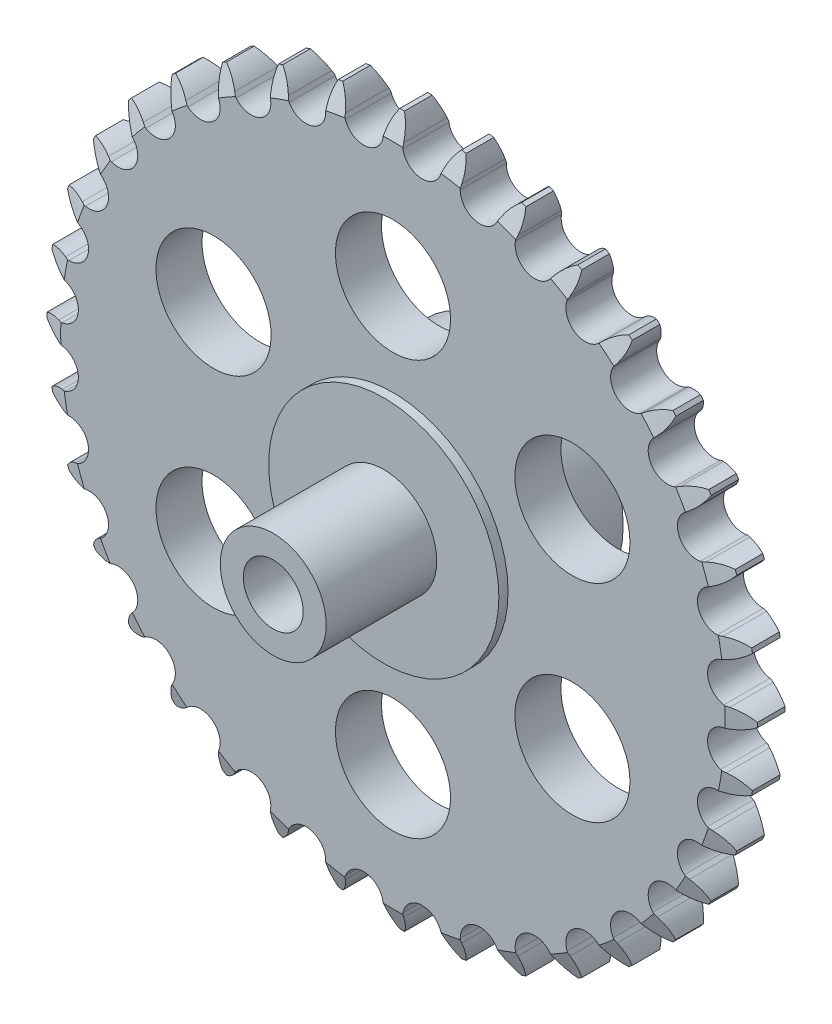
SolidWorks part; units mm, degrees
ref_plane "Front Plane" through (0, 0, 0) normal (0, 0, 1) x (1, 0, 0)
ref_plane "Top Plane" through (0, 0, 0) normal (0, 1, 0) x (1, 0, 0)
ref_plane "Right Plane" through (0, 0, 0) normal (1, 0, 0) x (0, 0, -1)
sketch "Sketch1" plane through (0, 0, 0) normal (0, 0, 1) x (1, 0, 0)
  line L0 (0, 0) -> (0, 72.8581) construction
  line L1 (-2.1568, 71.8581) -> (2.1568, 71.8581) construction
  line L2 (-2.1568, 71.8581) -> (-2.0429, 72.8581) construction
  line L3 (2.1568, 71.8581) -> (2.0429, 72.8581) construction
  line L4 (-2.0429, 72.8581) -> (2.0429, 72.8581) construction
  line L7 (-0.5, 77.163) -> (0.5, 77.163) construction
  circle A0 centre (0, 0) radius 72.8581 construction
  circle A1 centre (6.35, 72.5808) radius 4.255 construction
  circle A2 centre (-6.35, 72.5808) radius 4.255 construction
  circle A3 centre (0, 0) radius 68.6031 construction
  arc A4 (-2.0429, 72.8581) -> (-0.5, 77.163) centre (7.8928, 71.726) cw construction
  arc A5 (2.0429, 72.8581) -> (0.5, 77.163) centre (-7.8928, 71.726) ccw construction
  dimension "D1" = 13
  dimension "SprocketPitchDiameter" = 145.7162
  dimension "RollerDia" = 8.51
  dimension "D4" = 10
  dimension "ChainPitch" = 12.7
  dimension "D2" = 1
  dimension "D3" = 1
  dimension "D5" = 1
sketch "Sketch2" plane through (0, 0, 0) normal (0, 0, 1) x (1, 0, 0)
  circle A0 centre (0, 0) radius 68.6031 construction
  circle A1 centre (0, 0) radius 68.6031
extrude "Boss-Extrude1" add sketch "Sketch2" along normal mid plane 10
sketch "Sketch4" plane through (0, 0, 0) normal (0, 0, 1) x (1, 0, 0)
  line L0 (-0.5, 77.163) -> (0.5, 77.163) construction
  line L1 (-2.1568, 71.8581) -> (-2.0429, 72.8581) construction
  line L2 (2.1568, 71.8581) -> (2.0429, 72.8581) construction
  line L3 (-0.5, 77.163) -> (0.5, 77.163)
  line L4 (-2.1568, 71.8581) -> (-2.0429, 72.8581)
  line L5 (2.1568, 71.8581) -> (2.0429, 72.8581)
  circle A0 centre (0, 0) radius 68.6031 construction
  circle A1 centre (6.35, 72.5808) radius 4.255 construction
  circle A2 centre (-6.35, 72.5808) radius 4.255 construction
  arc A3 (2.0429, 72.8581) -> (0.5, 77.163) centre (-7.8928, 71.726) ccw construction
  arc A4 (-0.5, 77.163) -> (-2.0429, 72.8581) centre (7.8928, 71.726) ccw construction
  arc A5 (5.9792, 68.342) -> (-5.9792, 68.342) centre (0, 0) ccw
  arc A6 (2.1568, 71.8581) -> (5.9792, 68.342) centre (6.35, 72.5808) ccw
  arc A7 (-5.9792, 68.342) -> (-2.1568, 71.8581) centre (-6.35, 72.5808) ccw
  arc A8 (2.0429, 72.8581) -> (0.5, 77.163) centre (-7.8928, 71.726) ccw
  arc A9 (-0.5, 77.163) -> (-2.0429, 72.8581) centre (7.8928, 71.726) ccw
extrude "Boss-Extrude2" add sketch "Sketch4" along normal up to surface and the other way up to surface up to face at (68.6031, 0, 5) other way up to face at (68.6031, 0, -5)
pattern_circular "CirPattern1" count 36 over 360 about axis through (0, 0, 5) along (0, 0, -1) of "Boss-Extrude2"
sketch "Sketch5" plane through (0, 0, 0) normal (1, 0, 0) x (0, 0, -1)
  line L0 (0, 0) -> (-6, 0) construction
  line L1 (0, 77.163) -> (0, 72.8581) construction
  line L2 (-6, 84.663) -> (6, 84.663)
  line L3 (-6, 84.663) -> (-6, 69.663)
  line L4 (-6, 69.663) -> (6, 69.663) construction
  line L5 (6, 84.663) -> (6, 69.663)
  line L6 (-6, 84.663) -> (6, 69.663) construction
  line L7 (-6, 69.663) -> (6, 84.663) construction
  line L8 (-6, 69.663) -> (0, 84.663)
  line L9 (6, 69.663) -> (0, 84.663)
  line L10 (0, 77.163) -> (0, 72.8581) construction
  point P1 (0, 77.163)
  dimension "D1" = 15
  dimension "D2" = 1
revolve "Cut-Revolve7" cut sketch "Sketch5" angle 360 about L0 region at (0, 79.663, -4) region at (0, 79.663, 4)
sketch "Sketch6" plane through (0, 0, 0) normal (0, 0, 1) x (1, 0, 0)
  circle A0 centre (0, 0) radius 25
  dimension "D1" = 50
extrude "Boss-Extrude3" add sketch "Sketch6" along normal blind 7 and the other way blind 20
sketch "Sketch7" plane through (0, 0, 0) normal (0, 0, 1) x (1, 0, 0)
  circle A0 centre (0, 0) radius 6.5
  dimension "D1" = 13
extrude "Cut-Extrude1" cut sketch "Sketch7" against normal through all both and the other way through all
sketch "Sketch8" plane through (0, 0, 7) normal (0, 0, 1) x (1, 0, 0)
  circle A1 centre (0, 0) radius 6.5 construction
  circle A2 centre (0, 0) radius 11.5
  circle A3 centre (0, 0) radius 11.5
  circle A4 centre (0, 0) radius 6.5
  dimension "D1" = 5
extrude "Boss-Extrude4" add sketch "Sketch8" along normal blind 24
sketch "Sketch9" plane through (0, 0, 5) normal (0, 0, 1) x (1, 0, 0)
  circle A0 centre (0, 45) radius 12.5
  dimension "D1" = 25
  dimension "D2" = 45
extrude "Cut-Extrude2" cut sketch "Sketch9" against normal through all
pattern_circular "CirPattern2" count 6 over 360 about axis through (0, 0, -20) along (0, 0, 1) of "Cut-Extrude2"
equation "\"ChainPitch\"=12.7"
equation "\"ChainPitch@Sketch1\"=\"ChainPitch\""
equation "\"SprocketPitchDiameter@Sketch1\" = \"ChainPitch\" / sin ( 180 / \"NumberOfTeeth\" )"
equation "\"NumberOfTeeth\"= 36"
equation "\"D1@CirPattern1\"=\"NumberOfTeeth\""
